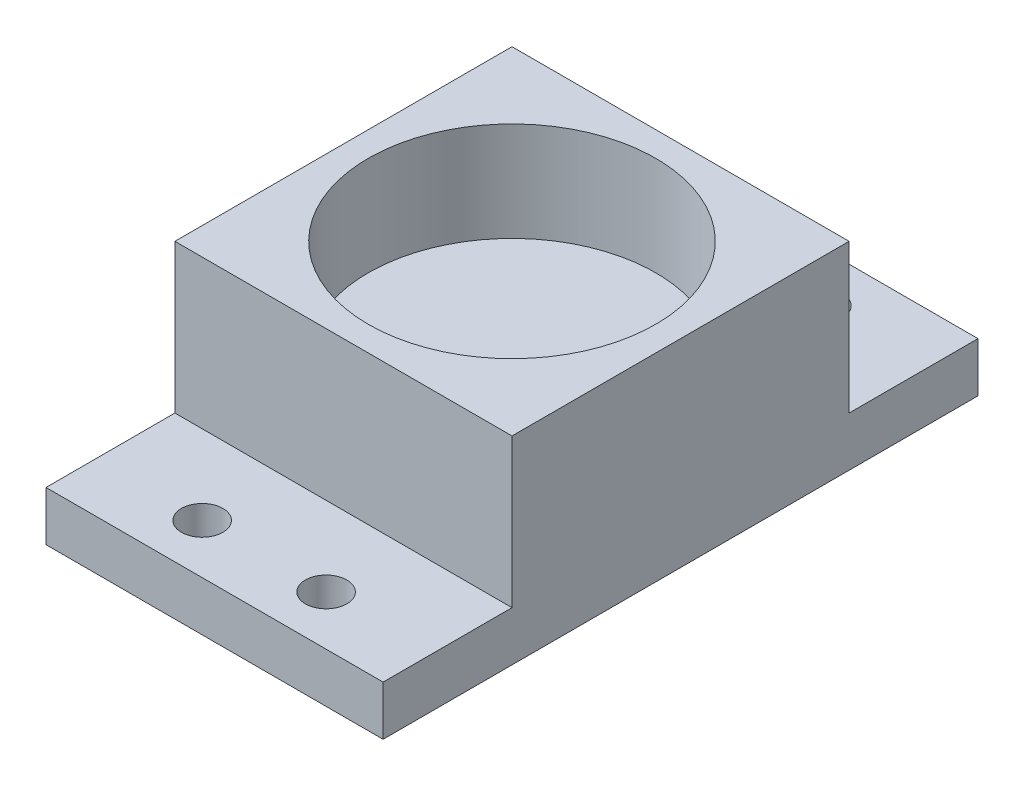
SolidWorks part; units mm, degrees
ref_plane "Front Plane" through (0, 0, 0) normal (0, 0, 1) x (1, 0, 0)
ref_plane "Top Plane" through (0, 0, 0) normal (0, 1, 0) x (1, 0, 0)
ref_plane "Right Plane" through (0, 0, 0) normal (1, 0, 0) x (0, 0, -1)
sketch "Sketch2" plane through (0, 0, 0) normal (0, 1, 0) x (1, 0, 0)
  line L1 (-38.1, -38.1) -> (38.1, -38.1)
  line L2 (-38.1, -38.1) -> (-38.1, 38.1)
  line L3 (-38.1, 38.1) -> (38.1, 38.1)
  line L4 (38.1, -38.1) -> (38.1, 38.1)
  line L5 (-38.1, -38.1) -> (38.1, 38.1) construction
  line L6 (-38.1, 38.1) -> (38.1, -38.1) construction
  circle A1 centre (0, 0) radius 38.1
  dimension "D1" = 76.2
extrude "Boss-Extrude1" add sketch "Sketch2" along normal blind 25.4 contours A1 L3 L2 | A1 | A1 L4 L3 | A1 L1 L4 | A1 L2 L1 region at (-29.5897, 0, 29.5897) region at (29.5897, 0, 29.5897) region at (0, 0, 0) region at (-29.5897, 0, -29.5897) region at (29.5897, 0, -29.5897)
sketch "Sketch3" plane through (0, 25.4, 0) normal (0, 1, 0) x (1, 0, 0)
  line L0 (-38.1, 38.1) -> (38.1, 38.1) construction
  line L2 (-21.59, -21.59) -> (21.59, -21.59)
  line L3 (-21.59, -21.59) -> (-21.59, 21.59)
  line L4 (-21.59, 21.59) -> (21.59, 21.59)
  line L5 (21.59, -21.59) -> (21.59, 21.59)
  line L6 (-21.59, -21.59) -> (21.59, 21.59) construction
  line L7 (-21.59, 21.59) -> (21.59, -21.59) construction
  circle A0 centre (0, 0) radius 18.415
  circle A1 centre (0, 0) radius 21.59
  circle A4 centre (0, 0) radius 38.1
  line M9 (-38.1, 38.1) -> (-38.1, -38.1)
  line M10 (-38.1, -38.1) -> (38.1, -38.1)
  line M11 (38.1, -38.1) -> (38.1, 38.1)
  line M12 (38.1, 38.1) -> (-38.1, 38.1)
  dimension "D1" = 36.83
  dimension "D2" = 3.175
extrude "Cut-Extrude1" cut sketch "Sketch3" against normal blind 12.7 contours A0
extrude "Cut-Extrude2" cut sketch "Sketch3<4>" against normal blind 19.05 contours A4 L5 L2 L3 L4 | A4 M9 M10 | A4 M12 M9 | A4 M11 M12 | A4 M10 M11 region at (26.1788, 25.4, 26.1788) region at (29.5897, 25.4, 29.5897) region at (29.5897, 25.4, -29.5897) region at (-29.5897, 25.4, -29.5897) region at (-29.5897, 25.4, 29.5897)
sketch "Sketch3<4>" plane through (0, 25.4, 0) normal (0, 1, 0) x (1, 0, 0) same geometry as "Sketch3"
sketch "Sketch5" plane through (0, 6.35, 0) normal (0, 1, 0) x (1, 0, 0)
  line L0 (38.1, 38.1) -> (-38.1, 38.1) construction
  line L5 (-21.59, -38.1) -> (21.59, -38.1)
  line L6 (-21.59, -38.1) -> (-21.59, 38.1)
  line L11 (-21.59, 38.1) -> (21.59, 38.1)
  line L12 (21.59, -38.1) -> (21.59, 38.1)
  line L13 (-21.59, -38.1) -> (21.59, 38.1) construction
  line L14 (-21.59, 38.1) -> (21.59, -38.1) construction
  line L15 (-21.59, -21.59) -> (-21.59, 21.59) construction
  line L16 (38.1, -38.1) -> (38.1, 38.1) construction
  line L17 (-38.1, -38.1) -> (38.1, -38.1) construction
  line L18 (-38.1, 38.1) -> (-38.1, -38.1) construction
  line L19 (38.1, -38.1) -> (38.1, 38.1)
  line L20 (-38.1, -38.1) -> (38.1, -38.1)
  line L21 (-38.1, 38.1) -> (-38.1, -38.1)
  line L22 (38.1, 38.1) -> (-38.1, 38.1)
  point P0 (0, 0)
extrude "Cut-Extrude3" cut sketch "Sketch5" against normal blind 12.7 contours L6 L22 L21 L20 | L19 L22 L12 L20 region at (-29.845, 6.35, 0) region at (29.845, 6.35, 0)
sketch "Sketch6" plane through (0, 6.35, 0) normal (0, 1, 0) x (1, 0, 0)
  line L0 (-18.415, 0) -> (21.59, 0) construction
  line L1 (0, 21.59) -> (0, -18.415) construction
  line L2 (-21.59, 21.59) -> (21.59, 21.59) construction
  line L3 (21.59, -21.59) -> (21.59, 21.59) construction
  circle A0 centre (0, 0) radius 18.415 construction
  point P4 (0, 0)
  point P5 (0, 0)
  point P7 (-7.9375, -31.75)
  point P8 (7.9375, -31.75)
  point P9 (-7.9375, 31.75)
  point P10 (7.9375, 31.75)
  point P11 (0, 0)
  point P12 (0, 0)
  point P13 (0, 0)
  point P17 (0, 0)
  point P20 (0, 0)
  dimension "D1" = 15.875
  dimension "D2" = 31.75
hole_wizard "#4 (0.209) Diameter Hole1" positions "Sketch7" profile "Sketch8" hole size "#4" standard "ANSI Inch" end condition up to next
sketch "Sketch7" plane through (0, 6.35, 0) normal (0, 1, 0) x (1, 0, 0)
  point P0 (7.9375, 31.75)
  point P3 (-7.9375, 31.75)
  point P6 (7.9375, -31.75)
  point P9 (-7.9375, -31.75)
sketch "Sketch8" plane through (7.9375, 6.35, -31.75) normal (1, 0, 0) x (0, 0, 1)
  line L0 (0, 0) -> (0, 6.35)
  line L1 (0, 6.35) -> (2.6543, 6.35)
  line L2 (2.6543, 6.35) -> (2.6543, 0)
  line L5 (2.6543, 0) -> (0, 0)
  line L11 (0, -6.35) -> (0, 107.95) construction
  dimension "Thru Hole Dia." = 5.3086
  dimension "Thru Hole Depth" = 6.35
